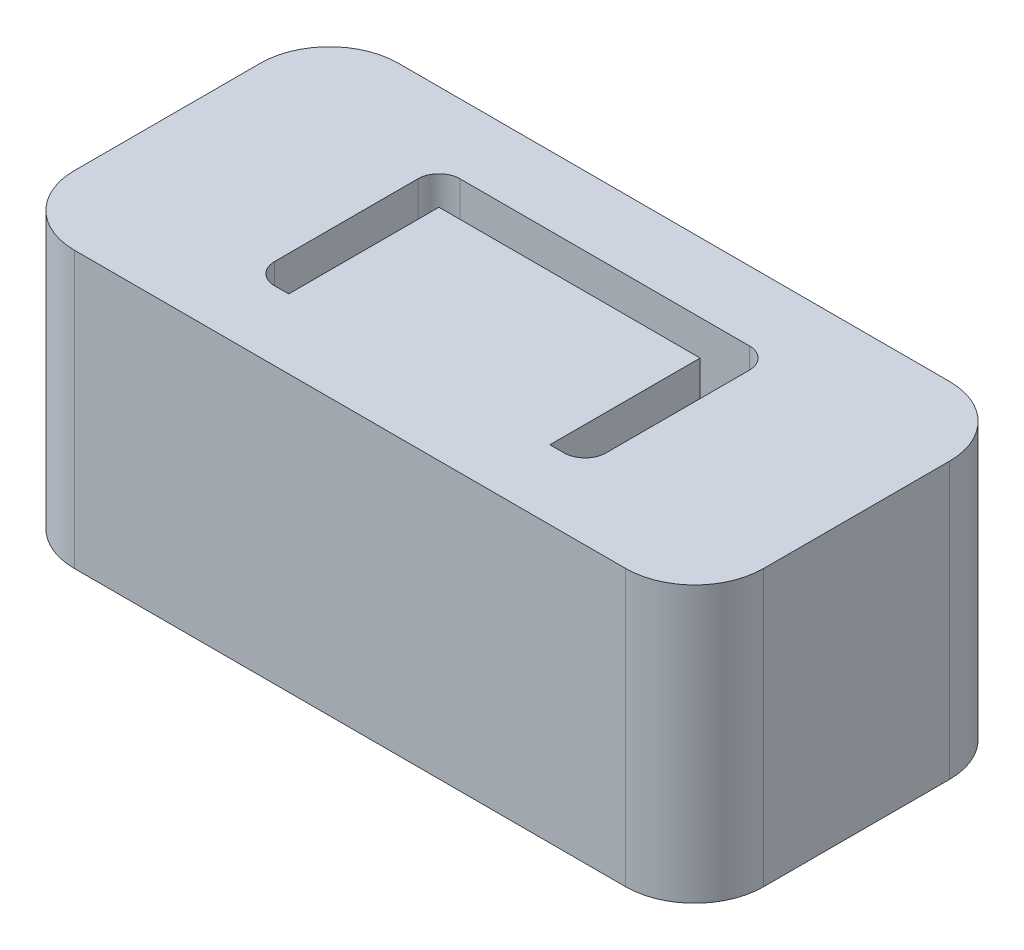
SolidWorks part; units mm, degrees
material "K110"
ref_plane "Front Plane" through (0, 0, 0) normal (0, 0, 1) x (1, 0, 0)
ref_plane "Top Plane" through (0, 0, 0) normal (0, 1, 0) x (1, 0, 0)
ref_plane "Right Plane" through (0, 0, 0) normal (1, 0, 0) x (0, 0, -1)
sketch "Sketch2" plane through (0, 0, 0) normal (0, 1, 0) x (1, 0, 0)
  line L1 (-50, -23.5) -> (50, -23.5)
  line L2 (-50, -23.5) -> (-50, 23.5)
  line L3 (-50, 23.5) -> (50, 23.5)
  line L4 (50, -23.5) -> (50, 23.5)
  line L5 (-50, -23.5) -> (50, 23.5) construction
  line L6 (-50, 23.5) -> (50, -23.5) construction
  point P0 (0, 0)
  dimension "D1" = 100
  dimension "D2" = 47
extrude "Boss-Extrude1" add sketch "Sketch2" against normal blind 40
fillet "Fillet1" radius 10 4 edges at (-50, -20, -23.5) (50, -20, -23.5) (50, -20, 23.5) (-50, -20, 23.5)
sketch "Sketch3" plane through (0, 0, 0) normal (0, 1, 0) x (1, 0, 0)
  line L16 (24.05, -10.4) -> (24.05, 10.4)
  line L17 (18.95, -13.45) -> (21, -13.45)
  line L18 (18.95, 8.35) -> (18.95, -13.45)
  line L19 (-18.95, 8.35) -> (18.95, 8.35)
  line L20 (-18.95, -13.45) -> (-18.95, 8.35)
  line L21 (-21, -13.45) -> (-18.95, -13.45)
  line L22 (-24.05, 10.4) -> (-24.05, -10.4)
  line L23 (21, 13.45) -> (-21, 13.45)
  line L24 (24.05, -10.4) -> (24.05, 10.4)
  line L25 (18.95, -13.45) -> (21, -13.45)
  line L26 (18.95, 8.35) -> (18.95, -13.45)
  line L27 (-18.95, 8.35) -> (18.95, 8.35)
  line L28 (-18.95, -13.45) -> (-18.95, 8.35)
  line L29 (-21, -13.45) -> (-18.95, -13.45)
  line L30 (-24.05, 10.4) -> (-24.05, -10.4)
  line L31 (21, 13.45) -> (-21, 13.45)
  arc A8 (24.05, 10.4) -> (21, 13.45) centre (21, 10.4) ccw
  arc A9 (21, -13.45) -> (24.05, -10.4) centre (21, -10.4) ccw
  arc A10 (-24.05, -10.4) -> (-21, -13.45) centre (-21, -10.4) ccw
  arc A11 (-21, 13.45) -> (-24.05, 10.4) centre (-21, 10.4) ccw
  arc A12 (24.05, 10.4) -> (21, 13.45) centre (21, 10.4) ccw
  arc A13 (21, -13.45) -> (24.05, -10.4) centre (21, -10.4) ccw
  arc A14 (-24.05, -10.4) -> (-21, -13.45) centre (-21, -10.4) ccw
  arc A15 (-21, 13.45) -> (-24.05, 10.4) centre (-21, 10.4) ccw
  dimension "D1" = 0.05
extrude "Cut-Extrude1" cut sketch "Sketch3" against normal up to next
hole_wizard "M6 Tapped Hole1" positions "Sketch6" profile "Sketch5" tap size "M6" standard "ISO"
sketch "Sketch6" plane through (0, -40, 0) normal (0, -1, 0) x (-1, 0, 0)
  line L0 (-50, -13.5) -> (-50, 13.5) construction
  line L1 (-40, 23.5) -> (40, 23.5) construction
  line L2 (40, -23.5) -> (-40, -23.5) construction
  line L3 (50, 13.5) -> (50, -13.5) construction
  point P0 (-43, 16.5)
  point P2 (43, 16.5)
  point P4 (43, -16.5)
  point P6 (-43, -16.5)
  dimension "D1" = 7
  dimension "D2" = 7
  dimension "D3" = 7
  dimension "D4" = 7
sketch "Sketch5" plane through (43, -40, -16.5) normal (1, 0, 0) x (0, 0, -1)
  line L0 (0, 0) -> (0, 18.5022)
  line L1 (0, 18.5022) -> (2.5, 17)
  line L2 (2.5, 17) -> (2.5, 0.525)
  line L3 (2.5, 0.525) -> (3.025, 0)
  line L5 (3.025, 0) -> (0, 0)
  line L6 (-2.5, 0.525) -> (-3.025, 0) construction
  line L10 (0, 18.5022) -> (-2.5, 17) construction
  line L11 (0, -6.35) -> (0, 107.95) construction
  dimension "Tap Drill Dia." = 5
  dimension "Tap Drill Depth" = 17
  dimension "Near C'Sink Dia." = 6.05
  dimension "Near C'Sink Angle" = 90
  dimension "Drill Angle" = 118
cosmetic thread "Hole Thread1"
cosmetic thread "Hole Thread2"
cosmetic thread "Hole Thread3"
cosmetic thread "Hole Thread4"
